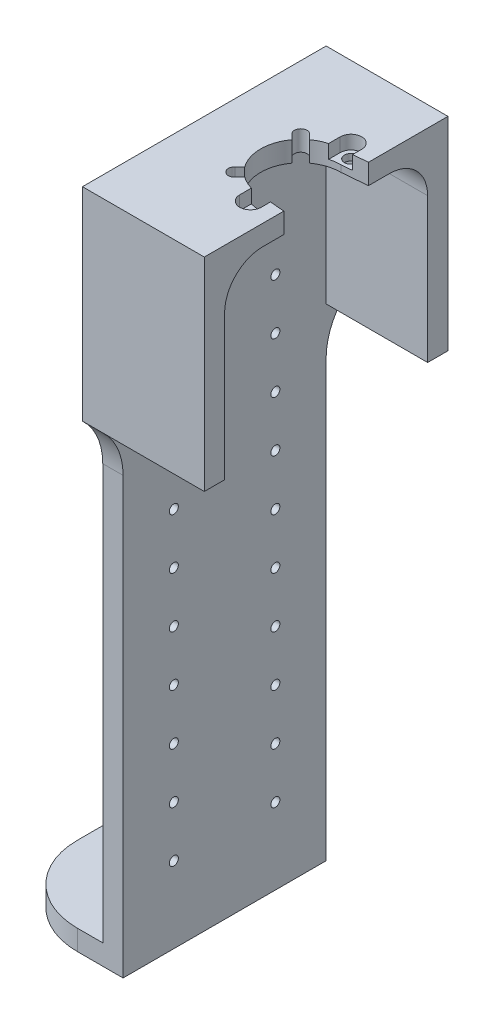
SolidWorks part; units mm, degrees
ref_plane "Front Plane" through (0, 0, 0) normal (0, 0, 1) x (1, 0, 0)
ref_plane "Top Plane" through (0, 0, 0) normal (0, 1, 0) x (1, 0, 0)
ref_plane "Right Plane" through (0, 0, 0) normal (1, 0, 0) x (0, 0, -1)
sketch "Sketch1" plane through (0, 0, 0) normal (0, 0, 1) x (1, 0, 0)
  line L0 (0, 0) -> (0, 131)
  line L1 (0, 131) -> (24, 131)
  line L2 (24, 131) -> (24, 127)
  line L3 (24, 127) -> (4, 127)
  line L4 (4, 127) -> (4, -4)
  line L5 (4, -4) -> (-20, -4)
  line L6 (-20, -4) -> (-20, 0)
  line L7 (-20, 0) -> (0, 0)
  dimension "D1" = 24
  dimension "D2" = 24
  dimension "D3" = 20
  dimension "D4" = 4
  dimension "D5" = 4
  dimension "D6" = 131
  dimension "D7" = 131
extrude "BracketMainBody" add sketch "Sketch1" along normal mid plane 40
sketch "M4_thruHole" plane through (0, -4, 0) normal (0, -1, 0) x (1, 0, 0)
  line L0 (-20, 20) -> (-20, -20) construction
  circle A0 centre (-10, 0) radius 2.4
  dimension "D1" = 4.8
  dimension "D2" = 10
  dimension "D3" = 10
sketch "SQUIDcutouts" plane through (0, 0, 0) normal (0, 1, 0) x (1, 0, 0)
  line L0 (24, -20) -> (24, 20) construction
  line L3 (0, -20) -> (0, 20) construction
  line L4 (24, 0) -> (4, 0) construction
  line L5 (12.6003, 4.6319) -> (11.6161, 5.6161)
  line L6 (13.3839, 7.3839) -> (14.3681, 6.3997)
  line L7 (11.6161, -5.6161) -> (12.6003, -4.6319)
  line L9 (13.3839, -7.3839) -> (14.3681, -6.3997)
  circle A0 centre (19, -9.9) radius 1.3
  circle A1 centre (19, 9.9) radius 1.3
  arc A2 (12.6003, 4.6319) -> (12.6003, -4.6319) centre (19, 0) ccw
  arc A3 (13.3839, 7.3839) -> (11.6161, 5.6161) centre (12.5, 6.5) ccw
  arc A4 (11.6161, -5.6161) -> (13.3839, -7.3839) centre (12.5, -6.5) ccw
  arc A5 (14.3681, -6.3997) -> (14.3681, 6.3997) centre (19, 0) ccw
  point P9 (8.775, 12.0934)
  point P12 (0, 0)
  point P13 (0, 0)
  point P24 (9.8217, 11.1962)
  dimension "D1" = 5
  dimension "D3" = 2.6
  dimension "D4" = 2.6
  dimension "D9" = 15.8
  dimension "D12" = 2.5
  dimension "D15" = 2.5
  dimension "D18" = 1.3919
  dimension "D2" = 9.9
  dimension "D5" = 5
  dimension "D6" = 9.9
  dimension "D7" = 5
  dimension "D10" = 6.5
  dimension "D11" = 12.5
  dimension "D13" = 6.5
  dimension "D14" = 12.5
  dimension "D16" = 1.3919
  dimension "D17" = 1.3919
  dimension "D19" = 7.9424
extrude "CutExtrude_SQUIDcutouts" cut sketch "SQUIDcutouts" against normal through all from surface contours A0 | A1 | A5 L6 A3 L5 A2 L7 A4 L9 starting at face at (12, 131, 0)
sketch "champhers" plane through (0, 131, 0) normal (0, 1, 0) x (1, 0, 0)
  line L0 (24, 8.3374) -> (24, 6.1164)
  line L1 (24, 6.1164) -> (24, 20) construction
  line L2 (24, 8.3374) -> (19, 7.9)
  line L4 (30.1328, 0) -> (13.0253, 0) construction
  line L5 (24, -6.1164) -> (19, -7.9)
  line L6 (24, -8.3374) -> (19, -7.9)
  line L7 (24, -8.3374) -> (24, -6.1164)
  line L9 (19, 7.9) -> (24, 6.1164)
  arc A0 (14.3681, -6.3997) -> (14.3681, 6.3997) centre (19, 0) ccw construction
  dimension "D2" = 85
extrude "Cut-Extrude7" [suppressed] cut sketch "champhers" against normal through all
sketch "Sketch11" plane through (0, 0, 20) normal (0, 0, 1) x (1, 0, 0)
  line L1 (0, 131) -> (24, 131)
  line L2 (0, 131) -> (0, 91)
  line L3 (0, 91) -> (24, 91)
  line L4 (24, 131) -> (24, 91)
  dimension "D1" = 40
  dimension "D2" = 24
extrude "Extrude_leftWall" add sketch "Sketch11" along normal blind 4
sketch "Sketch12" plane through (0, 0, -20) normal (0, 0, -1) x (-1, 0, 0)
  line L1 (-24, 91) -> (0, 91)
  line L2 (-24, 91) -> (-24, 131)
  line L3 (-24, 131) -> (0, 131)
  line L4 (0, 91) -> (0, 131)
  dimension "D1" = 40
  dimension "D2" = 24
extrude "Extrude_rightWall" add sketch "Sketch12" along normal blind 4
sketch "Sketch13" plane through (0, 131, 0) normal (0, 1, 0) x (1, 0, 0)
  line L0 (19, 9.9) -> (19, -9.9) construction
  line L5 (21.1241, 9.9) -> (21.1241, -9.9)
  line L6 (16.8759, 9.9) -> (16.8759, -9.9)
  arc A3 (21.1241, 9.9) -> (16.8759, 9.9) centre (19, 9.9) ccw
  arc A4 (16.8759, -9.9) -> (21.1241, -9.9) centre (19, -9.9) ccw
  point P3 (19, 0)
  dimension "D1" = 19.8
  dimension "D2" = 2.1241
ref_plane "M2CounterBore_offsetTopPlane" through (0, 128.3, 0) normal (0, 1, 0) x (1, 0, 0)
hole_wizard "M4 Clearance Hole1" positions "3DSketch1" profile "Sketch18" hole size "M4" standard "ANSI Metric" end condition up to next
sketch3d "3DSketch1"
  point P0 (-10, -4, 0)
sketch "Sketch18" plane through (-10, -4, 0) normal (1, 0, 0) x (0, 0, -1)
  line L0 (0, 0) -> (0, 4)
  line L1 (0, 4) -> (2.25, 4)
  line L2 (2.25, 4) -> (2.25, 0)
  line L5 (2.25, 0) -> (0, 0)
  line L11 (0, -6.35) -> (0, 107.95) construction
  dimension "Thru Hole Dia." = 4.5
  dimension "Thru Hole Depth" = 4
extrude "Cut-Extrude12" cut sketch "champhers<2>" against normal up to next
sketch "champhers<2>" plane through (0, 131, 0) normal (0, 1, 0) x (1, 0, 0) same geometry as "champhers"
fillet "Fillet2" radius 7.54 1 edges at (14, 127, 20)
fillet "Fillet3" radius 7.54 1 edges at (14, 127, -20)
fillet "Fillet4" radius 12.7 1 edges at (2, 91, -20)
fillet "Fillet5" radius 12.7 1 edges at (2, 91, 20)
fillet "Fillet11" radius 15 1 edges at (-20, -2, -20)
fillet "Fillet12" radius 15 1 edges at (-20, -2, 20)
fillet "Fillet13" [suppressed] radius 7.54
sketch "Sketch24" plane through (0, 0, 0) normal (1, 0, 0) x (0, 0, -1)
  line L0 (0, 0) -> (0, 131) construction
  line L1 (-24, 131) -> (24, 131) construction
  point P0 (10, 121)
  dimension "D1" = 10
  dimension "D2" = 10
hole_wizard "#2-56 Tapped Hole1" positions "3DSketch5" profile "Sketch25" tap size "#2-56" standard "ANSI Inch" end condition up to next
sketch3d "3DSketch5"
  line L0 (0, 0, 0) -> (0, 131, 0) construction
  line L1 (0, 131, 24) -> (0, 131, -24) construction
  point P4 (0, 121, -10)
  dimension "D1" = 10
  dimension "D2" = 10
sketch "Sketch25" plane through (0, 121, -10) normal (0, 1, 0) x (0, 0, 1)
  line L0 (0, 0) -> (0, 4.001)
  line L1 (0, 4.001) -> (0.889, 4.001)
  line L2 (0.889, 4.001) -> (0.889, 0)
  line L5 (0.889, 0) -> (0, 0)
  line L11 (0, -6.35) -> (0, 107.95) construction
  dimension "Thru Tap Drill Dia." = 1.778
  dimension "Thru Tap Drill Depth" = 4.001
cosmetic thread "Hole Thread2" parameters "D2"=2.1844
pattern_linear "LPattern3" count 12 spacing 10 along (0, -1, 0) count 2 spacing 20 along (0, 0, 1) of "#2-56 Tapped Hole1"
cosmetic thread "Hole Thread3" parameters "D2"=2.1844
cosmetic thread "Hole Thread4" parameters "D2"=2.1844
cosmetic thread "Hole Thread5" parameters "D2"=2.1844
cosmetic thread "Hole Thread6" parameters "D2"=2.1844
cosmetic thread "Hole Thread7" parameters "D2"=2.1844
cosmetic thread "Hole Thread8" parameters "D2"=2.1844
cosmetic thread "Hole Thread9" parameters "D2"=2.1844
cosmetic thread "Hole Thread10" parameters "D2"=2.1844
cosmetic thread "Hole Thread11" parameters "D2"=2.1844
cosmetic thread "Hole Thread12" parameters "D2"=2.1844
cosmetic thread "Hole Thread13" parameters "D2"=2.1844
cosmetic thread "Hole Thread14" parameters "D2"=2.1844
cosmetic thread "Hole Thread15" parameters "D2"=2.1844
cosmetic thread "Hole Thread16" parameters "D2"=2.1844
cosmetic thread "Hole Thread17" parameters "D2"=2.1844
cosmetic thread "Hole Thread18" parameters "D2"=2.1844
cosmetic thread "Hole Thread19" parameters "D2"=2.1844
cosmetic thread "Hole Thread20" parameters "D2"=2.1844
cosmetic thread "Hole Thread21" parameters "D2"=2.1844
cosmetic thread "Hole Thread22" parameters "D2"=2.1844
cosmetic thread "Hole Thread23" parameters "D2"=2.1844
cosmetic thread "Hole Thread24" parameters "D2"=2.1844
cosmetic thread "Hole Thread25" parameters "D2"=2.1844
fillet "Fillet15" [suppressed] radius 3.8
fillet "Fillet16" [suppressed] radius 7.54
fillet "Fillet17" [suppressed] radius 7.54
extrude "Cut-Extrude14" cut sketch "Sketch13" against normal up to surface (2.7 mm away) contours L5 A4 L6 A3 up to plane "M2CounterBore_offsetTopPlane"
